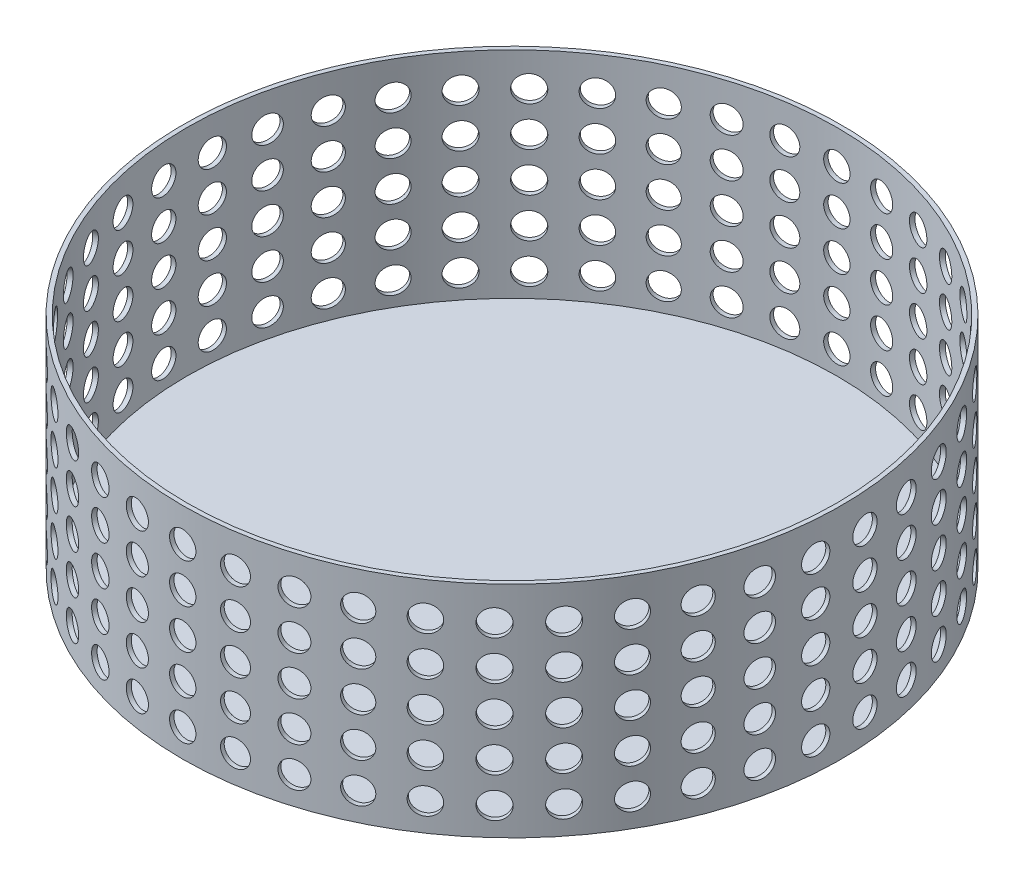
SolidWorks part; units mm, degrees
ref_plane "Front Plane" through (0, 0, 0) normal (0, 0, 1) x (1, 0, 0)
ref_plane "Top Plane" through (0, 0, 0) normal (0, 1, 0) x (1, 0, 0)
ref_plane "Right Plane" through (0, 0, 0) normal (1, 0, 0) x (0, 0, -1)
sketch "Sketch1" plane through (0, 0, 0) normal (0, 1, 0) x (1, 0, 0)
  circle A0 centre (0, 0) radius 75
  dimension "D1" = 150
extrude "Boss-Extrude1" add sketch "Sketch1" along normal blind 50
shell "Shell1" thickness 1
sketch "Sketch2" plane through (0, 0, 0) normal (0, 0, 1) x (1, 0, 0)
  circle A0 centre (0, 6.3476) radius 3
  circle A1 centre (0, 15.3476) radius 3
  circle A2 centre (0, 24.3476) radius 3
  circle A3 centre (0, 33.3476) radius 3
  circle A4 centre (0, 42.3476) radius 3
  dimension "D1" = 6
  dimension "D2" = 5
extrude "Cut-Extrude1" cut sketch "Sketch2" against normal through all and the other way through all
pattern_circular "CirPattern1" count 21 over 360 about axis through (0, 50, 0) along (0, -1, 0) of "Cut-Extrude1"
